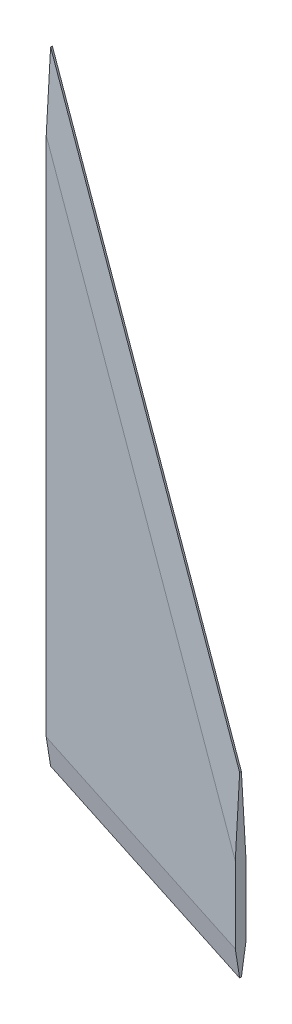
SolidWorks part; units mm, degrees
material "Hexcel AS4C (3000 Filaments)"
ref_plane "Front Plane" through (0, 0, 0) normal (0, 0, 1) x (1, 0, 0)
ref_plane "Top Plane" through (0, 0, 0) normal (0, 1, 0) x (1, 0, 0)
ref_plane "Right Plane" through (0, 0, 0) normal (1, 0, 0) x (0, 0, -1)
sketch "Sketch1" plane through (0, 0, 0) normal (0, 0, 1) x (1, 0, 0)
  line L0 (-16.41, -42.1531) -> (-16.41, 135.6469)
  line L1 (-16.41, 135.6469) -> (37.565, -16.7531)
  line L2 (37.565, -16.7531) -> (37.565, -67.5531)
  line L3 (37.565, -67.5531) -> (-16.41, -42.1531)
extrude "Boss-Extrude1" add sketch "Sketch1" along normal mid plane 3
chamfer "Chamfer1" distance 1.25 angle 80 4 edges at (10.5775, -54.8531, -1.5) (10.5775, -54.8531, 1.5) (10.5775, 59.4469, -1.5) (10.5775, 59.4469, 1.5) first distance on face at (10.5775, -54.8531, 0) first distance on face at (10.5775, 59.4469, 0)
